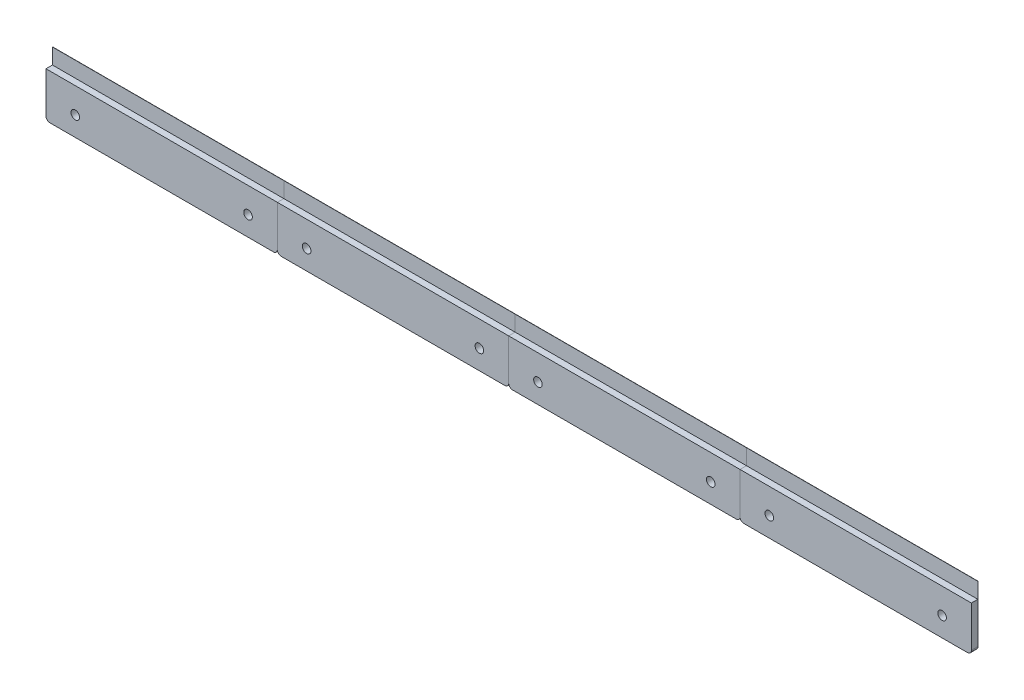
SolidWorks part; units mm, degrees
note: The reader was unsure of these and kept them because the rebuilt part matched: shared geometry of "Sketch1<3>".
ref_plane "Front Plane" through (0, 0, 0) normal (0, 0, 1) x (1, 0, 0)
ref_plane "Top Plane" through (0, 0, 0) normal (0, 1, 0) x (1, 0, 0)
ref_plane "Right Plane" through (0, 0, 0) normal (1, 0, 0) x (0, 0, -1)
sketch "Sketch1" plane through (0, 0, 0) normal (0, 0, 1) x (1, 0, 0)
  line L0 (-103.5, 10) -> (-15, 10) construction
  line L1 (0, 0) -> (-118.5, 0)
  line L2 (0, 0) -> (0, 23)
  line L3 (0, 23) -> (-118.5, 23)
  line L4 (-118.5, 0) -> (-118.5, 23)
  line L5 (-118.5, 23) -> (0, 23)
  line L6 (-118.5, 23) -> (-118.5, 31)
  line L7 (-118.5, 31) -> (0, 31)
  line L8 (0, 23) -> (0, 31)
  line L9 (-59.25, 20) -> (-59.25, 0) construction
  circle A0 centre (-103.5, 10) radius 2.2
  circle A1 centre (-15, 10) radius 2.2
  point P11 (-59.25, 10)
  point P14 (-99.6301, 15)
  point P15 (-57.5, 19.7623)
  dimension "D4" = 4.4
  dimension "D1" = 118.5
  dimension "D2" = 23
  dimension "D3" = 8
  dimension "D5" = 15
  dimension "D6" = 20
extrude "Boss-Extrude1" add sketch "Sketch1" along normal blind 4 contours L4 L1 L2 L3 A1 A0
extrude "Boss-Extrude2" add sketch "Sketch1<3>" along normal blind 0.7 contours L3 L8 L7 L6
sketch "Sketch1<3>" plane through (0, 0, 0) normal (0, 0, 1) x (1, 0, 0) same geometry as "Sketch1"
mirror "Mirror1" about plane through (0, 0, 4) normal (-1, 0, 0) of bodies 102
mirror "Mirror2" about plane through (-118.5, 0, 4) normal (-1, 0, 0) of bodies 102 103
fillet "Fillet2" radius 2 2 edges at (0, 0, 2) (-118.5, 0, 2)
fillet "Fillet3" radius 2 2 edges at (0, 0, 2) (118.5, 0, 2)
fillet "Fillet5" radius 2 2 edges at (-237, 0, 2) (-355.5, 0, 2)
fillet "Fillet6" radius 2 2 edges at (-237, 0, 2) (-118.5, 0, 2)
chamfer "Chamfer6" distance 0.6 angle 45 8 edges at (-338.3, 10, 0) (-249.8, 10, 0) (-296.25, 31, 0) (-296.25, 0, 0) (-355.5, 16.5, 0) (-237, 16.5, 0) (-237.5858, 0.5858, 0) (-354.9142, 0.5858, 0)
chamfer "Chamfer5" distance 0.6 angle 45 8 edges at (-135.7, 10, 0) (-224.2, 10, 0) (-177.75, 31, 0) (-118.5, 16.5, 0) (-177.75, 0, 0) (-237, 16.5, 0) (-236.4142, 0.5858, 0) (-119.0858, 0.5858, 0)
chamfer "Chamfer3" distance 0.6 angle 45 8 edges at (101.3, 10, 0) (12.8, 10, 0) (59.25, 31, 0) (118.5, 16.5, 0) (59.25, 0, 0) (0, 16.5, 0) (0.5858, 0.5858, 0) (117.9142, 0.5858, 0)
chamfer "Chamfer4" distance 0.6 angle 45 8 edges at (-59.25, 0, 0) (0, 16.5, 0) (-59.25, 31, 0) (-118.5, 16.5, 0) (-101.3, 10, 0) (-12.8, 10, 0) (-117.9142, 0.5858, 0) (-0.5858, 0.5858, 0)
